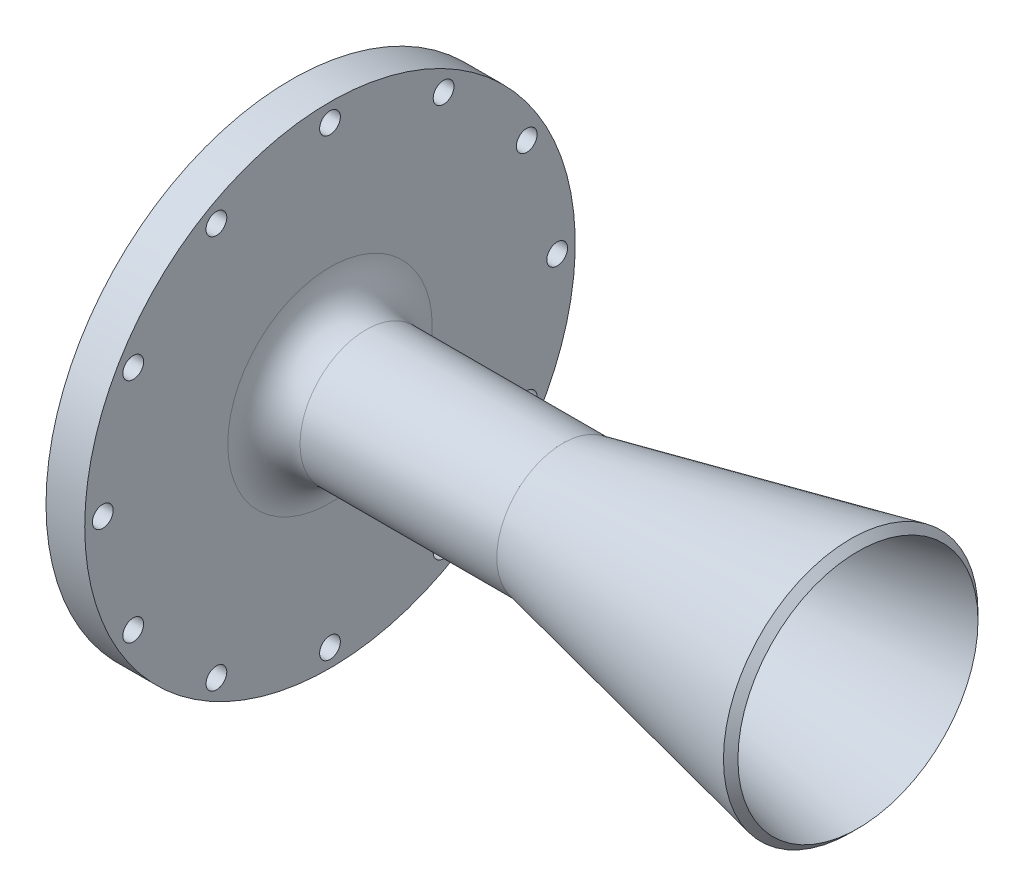
SolidWorks part; units mm, degrees
material "Stainless Steel (ferritic)"
ref_plane "Front Plane" through (0, 0, 0) normal (0, 0, 1) x (1, 0, 0)
ref_plane "Top Plane" through (0, 0, 0) normal (0, 1, 0) x (1, 0, 0)
ref_plane "Right Plane" through (0, 0, 0) normal (1, 0, 0) x (0, 0, -1)
sketch "Sketch2" plane through (0, 0, 0) normal (0, 0, 1) x (1, 0, 0)
  line L0 (0, 0) -> (165.0115, 0) construction
  line L1 (0, 20.5835) -> (0, 60.325)
  line L2 (0, 60.325) -> (9.525, 60.325)
  line L3 (9.525, 60.325) -> (9.525, 16.256)
  line L11 (66.8065, 16.256) -> (139.7, 31.75)
  line L17 (139.7, 31.75) -> (139.7, 29.5925)
  line L18 (60.325, 12.7208) -> (60.325, 14.351)
  line L19 (60.325, 14.351) -> (10.795, 14.351)
  line L20 (0, 20.5835) -> (10.795, 14.351)
  line L21 (60.325, 12.7208) -> (139.7, 29.5925)
  line L22 (9.525, 16.256) -> (66.8065, 16.256)
  dimension "D2" = 9.525
  dimension "D3" = 1.905
  dimension "D4" = 10.795
  dimension "D5" = 14.351
  dimension "D6" = 31.75
  dimension "D7" = 12
  dimension "D8" = 139.7
  dimension "D9" = 1.6302
  dimension "D10" = 30
  dimension "D11" = 60.325
  dimension "D12" = 49.53
revolve "Main Structure" add sketch "Sketch2" angle 360 about L0
sketch "Sketch4" plane through (0, 0, 0) normal (-1, 0, 0) x (0, 0, 1)
  circle A0 centre (0, 0) radius 55.88 construction
  circle A1 centre (0, -55.88) radius 2.146
  circle A2 centre (-27.94, -48.3935) radius 2.146
  circle A3 centre (-48.3935, -27.94) radius 2.146
  circle A4 centre (-55.88, 0) radius 2.146
  circle A5 centre (-48.3935, 27.94) radius 2.146
  circle A6 centre (-27.94, 48.3935) radius 2.146
  circle A7 centre (0, 55.88) radius 2.146
  circle A8 centre (27.94, 48.3935) radius 2.146
  circle A9 centre (48.3935, 27.94) radius 2.146
  circle A10 centre (55.88, 0) radius 2.146
  circle A11 centre (48.3935, -27.94) radius 2.146
  circle A12 centre (27.94, -48.3935) radius 2.146
  point P29 (0, 0)
  dimension "D1" = 12
  dimension "D2" = 111.76
hole_wizard "Flange Holes" positions "Sketch7" profile "Sketch8" hole size "#7" standard "ANSI Inch" end condition up to next
sketch "Sketch7" plane through (0, 0, 0) normal (-1, 0, 0) x (0, 0, 1)
  point P0 (0, -55.88)
  point P3 (-27.94, -48.3935)
  point P6 (-48.3935, -27.94)
  point P9 (-55.88, 0)
  point P12 (-48.3935, 27.94)
  point P15 (-27.94, 48.3935)
  point P18 (0, 55.88)
  point P21 (27.94, 48.3935)
  point P24 (48.3935, 27.94)
  point P27 (55.88, 0)
  point P30 (48.3935, -27.94)
  point P33 (27.94, -48.3935)
sketch "Sketch8" plane through (0, -55.88, 0) normal (0, 1, 0) x (0, 0, 1)
  line L0 (0, 0) -> (0, 9.525)
  line L1 (0, 9.525) -> (2.5527, 9.525)
  line L2 (2.5527, 9.525) -> (2.5527, 0)
  line L5 (2.5527, 0) -> (0, 0)
  line L11 (0, -6.35) -> (0, 107.95) construction
  dimension "Thru Hole Dia." = 5.1054
  dimension "Thru Hole Depth" = 9.525
sketch "Sketch9" plane through (0, 0, 0) normal (-1, 0, 0) x (0, 0, 1)
  line L0 (0, 0) -> (-67.6727, 18.1329) construction
  line L1 (0, 0) -> (-55.88, 0) construction
  circle A0 centre (0, 0) radius 55.88 construction
  circle A1 centre (-53.9759, 14.4628) radius 2.9451
  circle A2 centre (53.9759, -14.4628) radius 2.9451
  point P14 (0, 0)
  dimension "D1" = 15
  dimension "D2" = 2
hole_wizard "Dowel Holes" positions "Sketch10" profile "Sketch11" hole size "3/16" standard "ANSI Inch"
sketch "Sketch10" plane through (0, 0, 0) normal (-1, 0, 0) x (0, 0, 1)
  point P0 (53.9759, -14.4628)
  point P3 (-53.9759, 14.4628)
sketch "Sketch11" plane through (0, -14.4628, 53.9759) normal (0, 1, 0) x (0, 0, 1)
  line L0 (0, 0) -> (0, 7.7808)
  line L1 (0, 7.7808) -> (2.3812, 6.35)
  line L2 (2.3812, 6.35) -> (2.3812, 0)
  line L5 (2.3812, 0) -> (0, 0)
  line L10 (0, 7.7808) -> (-2.3812, 6.35) construction
  line L11 (0, -6.35) -> (0, 107.95) construction
  dimension "Hole Dia." = 4.7625
  dimension "Hole Depth" = 6.35
  dimension "Drill Angle" = 118
fillet "Fillet1" radius 8.89 1 edges at (9.525, 0, 16.256)
sketch "Sketch13" plane through (0, 0, 0) normal (0, 1, 0) x (1, 0, 0)
  line L0 (0, 36) -> (3.1496, 0)
  line L1 (0, 60.325) -> (0, -60.325) construction
  line L2 (3.1496, 0) -> (0, 0)
  line L3 (0, 0) -> (0, 36)
  dimension "D1" = 36
  dimension "D2" = 5
revolve "Cut-Revolve1" cut sketch "Sketch13" angle 360 about L2
chamfer "Chamfer1" distance 2.54 angle 45 1 edges at (139.7, 0, 31.75) first distance on face at (139.7, 0, 31.75)
